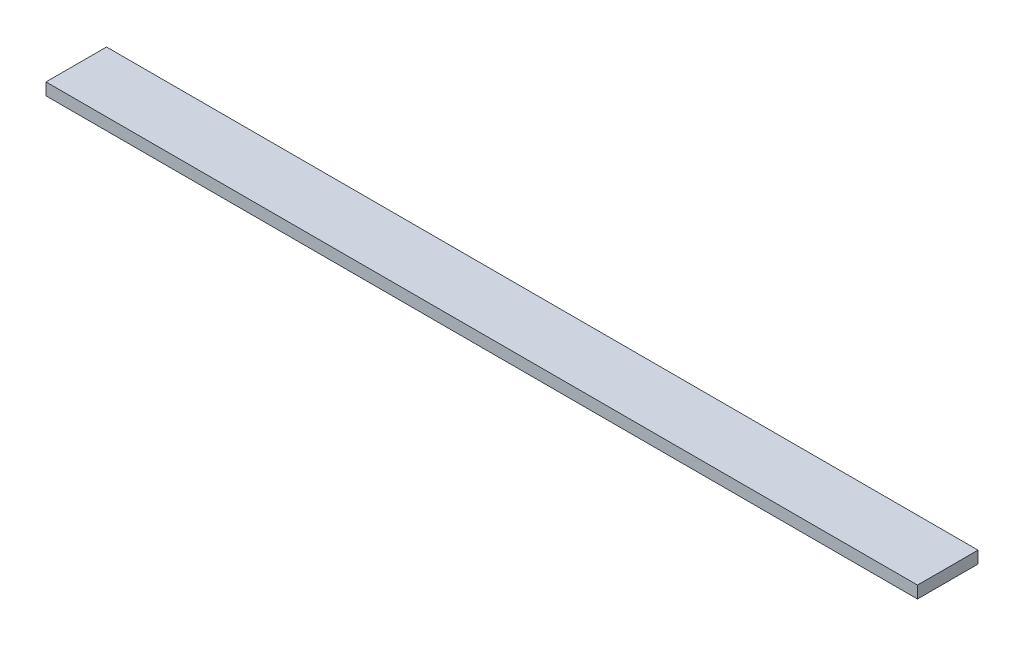
SolidWorks part; units mm, degrees
ref_plane "Front Plane" through (0, 0, 0) normal (0, 0, 1) x (1, 0, 0)
ref_plane "Top Plane" through (0, 0, 0) normal (0, 1, 0) x (1, 0, 0)
ref_plane "Right Plane" through (0, 0, 0) normal (1, 0, 0) x (0, 0, -1)
sketch "Sketch1" plane through (0, 0, 0) normal (0, 1, 0) x (1, 0, 0)
  line L1 (0, 0) -> (914.4, 0)
  line L2 (0, 0) -> (0, 63.5)
  line L3 (0, 63.5) -> (914.4, 63.5)
  line L4 (914.4, 0) -> (914.4, 63.5)
  dimension "D1" = 63.5
  dimension "D2" = 914.4
extrude "Boss-Extrude1" add sketch "Sketch1" along normal blind 12.7
